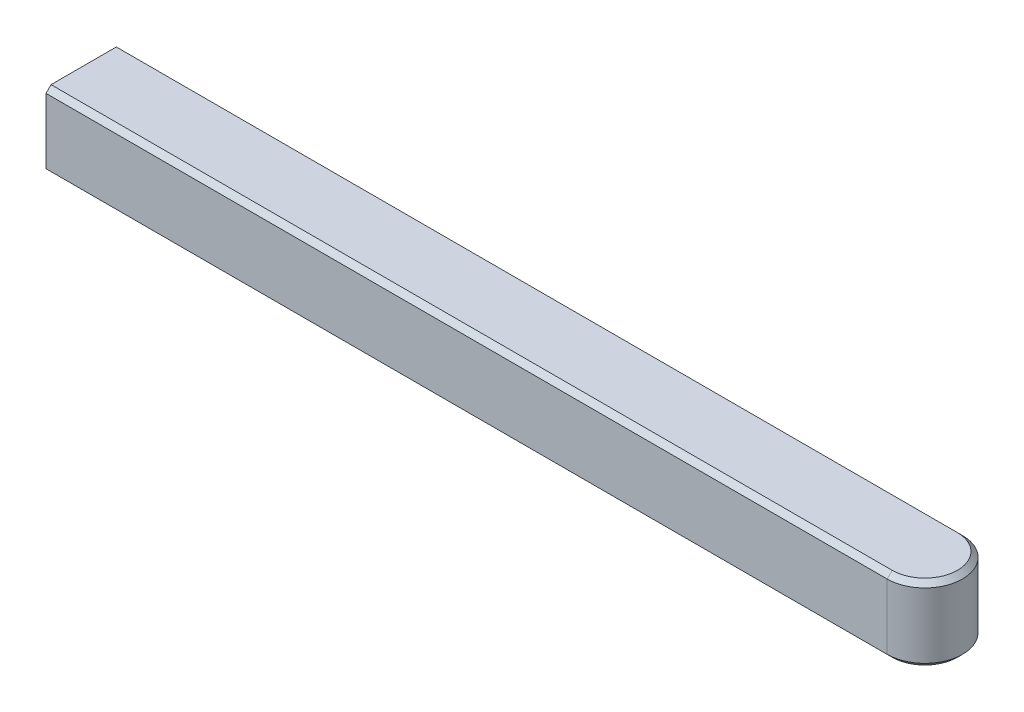
SolidWorks part; units mm, degrees
material "S45C"
ref_plane "Front Plane" through (0, 0, 0) normal (0, 0, 1) x (1, 0, 0)
ref_plane "Top Plane" through (0, 0, 0) normal (0, 1, 0) x (1, 0, 0)
ref_plane "Right Plane" through (0, 0, 0) normal (1, 0, 0) x (0, 0, -1)
sketch "Sketch1" plane through (0, 0, 0) normal (0, 1, 0) x (1, 0, 0)
  line L0 (-17.5, 0) -> (17.5, 0) construction
  line L1 (0, 1.5) -> (0, -1.5) construction
  line L3 (-17.5, 1.5) -> (17.5, 1.5)
  line L4 (-17.5, 1.5) -> (-17.5, -1.5)
  line L5 (-17.5, -1.5) -> (17.5, -1.5)
  line L6 (17.5, 1.5) -> (17.5, -1.5)
  dimension "L" = 35
  dimension "B" = 3
extrude "Boss-Extrude1" add sketch "Sketch1" along normal blind 3
chamfer "Chamfer1" [suppressed] distance 0.2 angle 45
fillet "Fillet1" [suppressed] type full round
fillet "Fillet2" 2 edges at (17.5, 1.5, 1.5) (17.5, 1.5, -1.5) type full round first side face at (0, 1.5, 1.5) second side face at (0, 1.5, -1.5) middle face at (17.5, 1.5, 0)
chamfer "Chamfer2" distance 0.2 angle 45 6 edges at (-0.75, 0, -1.5) (17.5, 0, 0) (-0.75, 0, 1.5) (-0.75, 3, -1.5) (17.5, 3, 0) (-0.75, 3, 1.5)
